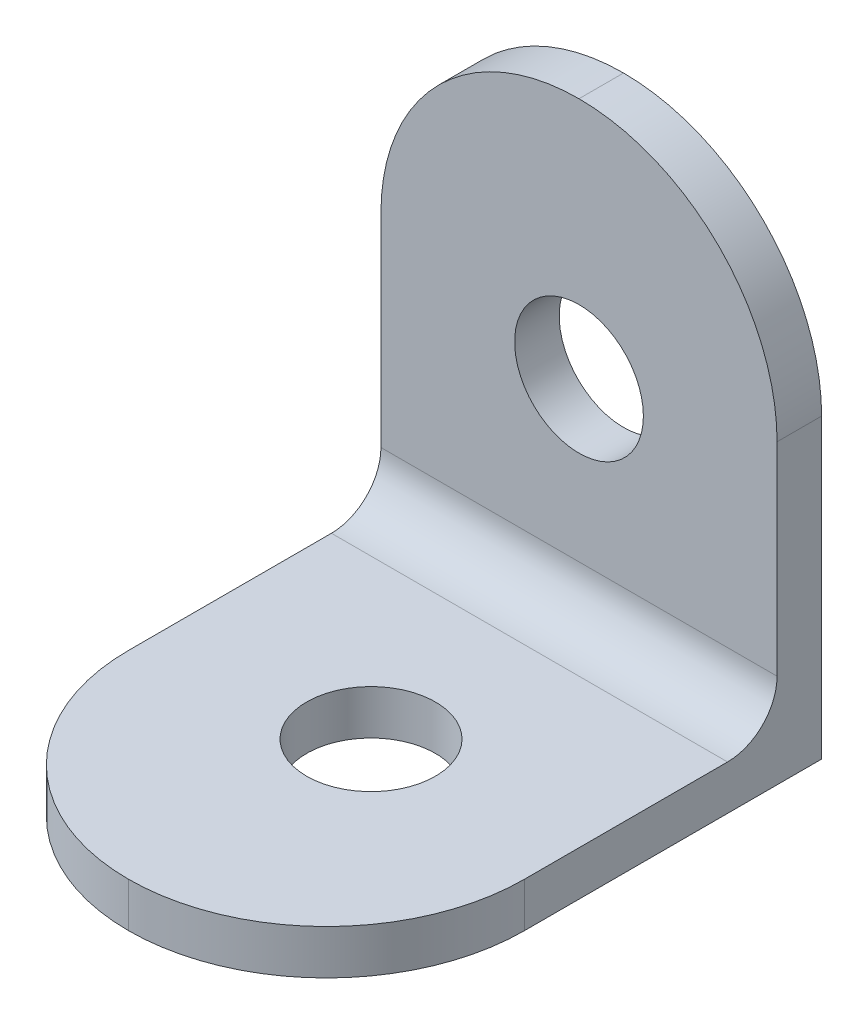
SolidWorks part; units mm, degrees
ref_plane "Front Plane" through (0, 0, 0) normal (0, 0, 1) x (1, 0, 0)
ref_plane "Top Plane" through (0, 0, 0) normal (0, 1, 0) x (1, 0, 0)
ref_plane "Right Plane" through (0, 0, 0) normal (1, 0, 0) x (0, 0, -1)
sketch "Sketch1" plane through (0, 0, 0) normal (0, 0, 1) x (1, 0, 0)
  line L1 (0, 0) -> (16, 0)
  line L2 (0, 0) -> (0, 20)
  line L3 (0, 20) -> (16, 20)
  line L4 (16, 0) -> (16, 20)
  dimension "D1" = 16
  dimension "D2" = 20
extrude "Boss-Extrude1" add sketch "Sketch1" along normal blind 1.8
sketch "Sketch2" plane through (0, 0, 0) normal (0, -1, 0) x (1, 0, 0)
  line L1 (0, 1.8) -> (16, 1.8)
  line L2 (0, 1.8) -> (0, 20)
  line L3 (0, 20) -> (16, 20)
  line L4 (16, 1.8) -> (16, 20)
  dimension "D1" = 18.2
  dimension "D2" = 16
extrude "Boss-Extrude2" add sketch "Sketch2" against normal blind 1.8
sketch "Sketch3" plane through (0, 0, 1.8) normal (0, 0, 1) x (1, 0, 0)
  line L0 (16, 1.8) -> (16, 20) construction
  line L2 (16, 0) -> (0, 0) construction
  circle A0 centre (8, 10.2) radius 2.6
  dimension "D1" = 5.2
  dimension "D2" = 8
  dimension "D3" = 10.2
extrude "Cut-Extrude1" cut sketch "Sketch3" against normal blind 1.8
sketch "Sketch4" plane through (0, 1.8, 0) normal (0, 1, 0) x (1, 0, 0)
  line L0 (16, -1.8) -> (16, -20) construction
  line L1 (16, 0) -> (0, 0) construction
  circle A0 centre (8, -10.2) radius 2.6
  dimension "D1" = 8
  dimension "D2" = 5.2
  dimension "D3" = 10.2
extrude "Cut-Extrude2" cut sketch "Sketch4" against normal blind 1.8
fillet "Fillet1" radius 2 1 edges at (8, 1.8, 1.8)
fillet "Fillet2" radius 8 4 edges at (16, 0.9, 20) (0, 0.9, 20) (16, 20, 0.9) (0, 20, 0.9)
